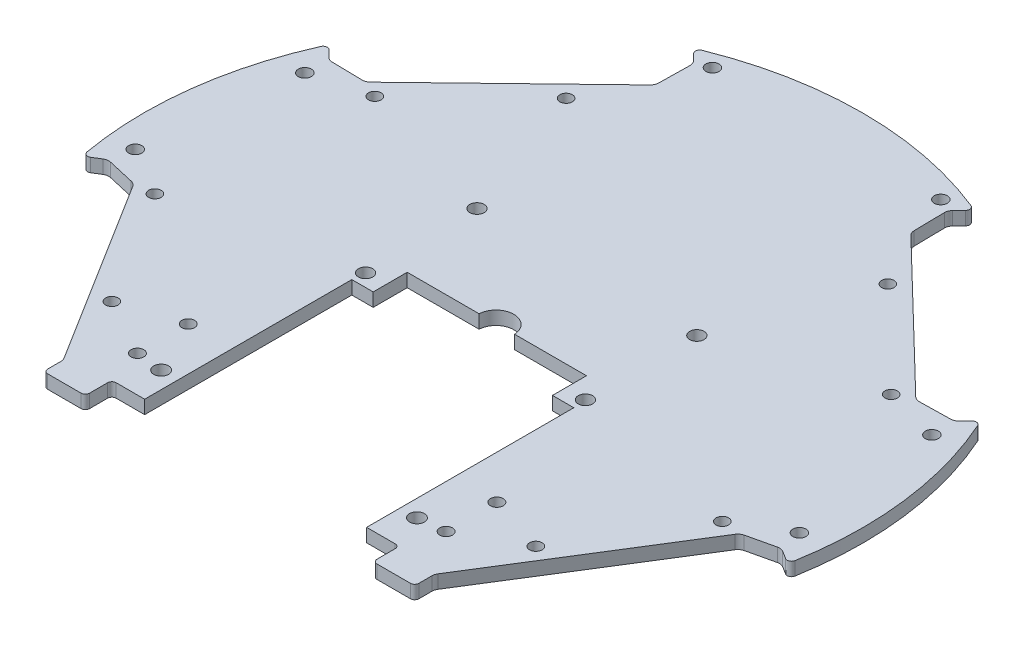
SolidWorks part; units mm, degrees
note: '?' marks a value the reader was unsure of.
material "6061 Alloy"
ref_plane "Front Plane" through (0, 0, 0) normal (0, 0, 1) x (1, 0, 0)
ref_plane "Top Plane" through (0, 0, 0) normal (0, 1, 0) x (1, 0, 0)
ref_plane "Right Plane" through (0, 0, 0) normal (1, 0, 0) x (0, 0, -1)
sketch "Sketch1" plane through (0, 0, 0) normal (0, 1, 0) x (1, 0, 0)
  line L0 (0, 0) -> (0, -59.55) construction
  line L1 (-83.4462, -16.178) -> (-71.2857, -8.5793) construction
  line L6 (0, 0) -> (-59.046, 61.1439) construction
  line L7 (0, 0) -> (-72.0841, -45.0431) construction
  line L8 (-33.174, 78.2591) -> (-23.2129, 67.9442) construction
  line L9 (-72.0841, -45.0431) -> (-70.388, -43.9833) construction
  line L10 (-70.388, -43.9833) -> (-84.9608, -20.662) construction
  line L11 (-84.9608, -20.662) -> (-72.2401, -12.7132) construction
  line L12 (-72.2401, -12.7132) -> (-43.0945, -59.3558) construction
  line L13 (-43.0945, -59.3558) -> (-55.8152, -67.3046) construction
  line L14 (-55.8152, -67.3046) -> (-70.388, -43.9833) construction
  line L21 (-59.046, 61.1439) -> (-57.6566, 59.7052)
  line L22 (-77.4385, 40.6021) -> (-37.8748, 78.8083) construction
  line L23 (-73.9694, 32.6911) -> (-77.0537, 35.885)
  line L24 (-37.8748, 78.8083) -> (-27.4549, 68.0182) construction
  line L25 (-27.4549, 68.0182) -> (-67.0186, 29.812) construction
  line L26 (-67.0186, 29.812) -> (-77.4385, 40.6021) construction
  line L27 (-43.0945, -64.8266) -> (-34, -64.8266)
  line L33 (-86.5505, -18.1178) -> (-71.2857, -8.5793) construction
  line L34 (0, 0) -> (0, 50000) construction
  line L35 (0, 0) -> (-50000, 0) construction
  line L36 (-60.6531, -59.55) -> (-19.8595, -59.55) construction
  line L38 (-67.0927, 25.57) -> (-79.5965, 38.5181) construction
  line L39 (-54.9774, -64.8266) -> (0, -64.8266) construction
  line L40 (-35.7168, 80.8923) -> (-23.2129, 67.9442) construction
  line L41 (-38.9606, -60.3102) -> (-54.2255, -69.8488) construction
  line L42 (-34, -59.55) -> (-19.8595, -59.55) construction
  line L43 (-43.0945, -64.8266) -> (-43.0945, -58.4123) construction
  line L45 (73.9694, 32.6911) -> (77.0537, 35.885)
  line L46 (-71.2857, -8.5793) -> (-38.9606, -60.3102) construction
  line L47 (83.4462, -16.178) -> (79.6809, -13.8252)
  line L48 (69.4846, -16.1792) -> (43.8945, -57.132)
  line L50 (43.0945, -64.8266) -> (34, -64.8266)
  line L51 (34, -59.55) -> (34, -64.8266)
  line L52 (0, 0) -> (72.0841, -45.0431) construction
  line L53 (0, 0) -> (59.046, 61.1439) construction
  line L54 (-30.0897, 75.0653) -> (-30.2847, 63.8954)
  line L55 (-62.7996, 32.4961) -> (-30.2847, 63.8954)
  line L56 (-30.0897, 75.0653) -> (-33.174, 78.2591)
  line L57 (73.9694, 32.6911) -> (77.0537, 35.885)
  line L58 (30.0897, 75.0653) -> (33.174, 78.2591)
  line L59 (-34, -59.55) -> (-34, -58.55)
  line L60 (62.7996, 32.4961) -> (30.2847, 63.8954)
  line L61 (-73.9694, 32.6911) -> (-62.7996, 32.4961)
  line L62 (-77.0537, 35.885) -> (-67.0927, 25.57) construction
  line L63 (-83.4462, -16.178) -> (-79.6809, -13.8252)
  line L64 (-79.6809, -13.8252) -> (-69.4846, -16.1792)
  line L65 (-69.4846, -16.1792) -> (-43.8945, -57.132)
  line L66 (-27.4549, 68.0182) -> (-23.2129, 67.9442) construction
  line L67 (-72.2401, -12.7132) -> (-71.2857, -8.5793) construction
  line L68 (30.0897, 75.0653) -> (30.2847, 63.8954)
  line L69 (73.9694, 32.6911) -> (62.7996, 32.4961)
  line L70 (-34, -59.55) -> (-34, -64.8266)
  line L71 (79.6809, -13.8252) -> (69.4846, -16.1792)
  line L72 (-34, -58.55) -> (-20, -58.55)
  line L73 (-20, -58.55) -> (-19.8595, -59.55)
  line L74 (-19.8595, -59.55) -> (19.8595, -59.55)
  line L75 (20, -58.55) -> (19.8595, -59.55)
  line L76 (34, -58.55) -> (20, -58.55)
  line L77 (34, -59.55) -> (34, -58.55)
  line L78 (-43.0945, -64.8266) -> (-43.8945, -64.8266)
  line L79 (-19.8595, -59.55) -> (0, -59.55) construction
  line L80 (-19.8595, -59.55) -> (34, -59.55) construction
  line L81 (-43.8945, -64.8266) -> (-43.8945, -57.132)
  line L82 (-43.0945, -58.4123) -> (-43.8945, -57.132) construction
  line L83 (43.8945, -64.8266) -> (43.8945, -57.132)
  line L84 (43.0945, -64.8266) -> (43.8945, -64.8266)
  line L97 (-23.2129, 67.9442) -> (-67.0927, 25.57) construction
  circle A0 centre (0, 0) radius 85 construction
  circle A1 centre (0, 0) radius 90 construction
  arc A51 (-77.0537, 35.885) -> (-83.4462, -16.178) centre (0, 0) ccw
  arc A52 (77.0537, 35.885) -> (83.4462, -16.178) centre (0, 0) cw
  arc A54 (-33.174, 78.2591) -> (33.174, 78.2591) centre (0, 0) cw
  point P29 (-31.6318, 76.6622)
  point P33 (-47.2368, 48.9151)
  point P34 (31.6318, 76.6622)
  point P35 (-57.6673, -36.0345)
  point P85 (-57.6566, 59.7052)
  dimension "D2" = 58
  dimension "D10" = 82
  dimension "D12" = 170
  dimension "D14" = 34
  dimension "D13" = 1
  dimension "D15" = 3
  dimension "D3" = 180
  dimension "D4" = 64.8266
  dimension "D5" = 44
  dimension "D6" = 15
  dimension "D7" = 55
  dimension "D8" = 59.55
  dimension "D9" = 2
  dimension "D11" = 2
  dimension "D16" = 7
  dimension "D17" = 7
  dimension "D18" = 0.5
  dimension "D19" = 1
  dimension "D20" = 14
  dimension "D21" = 0.8
extrude "Boss-Extrude4" add sketch "Sketch1" along normal mid plane 3.175
ref_point "Rear_Axle_Center (L)"
ref_axis "Rear_Axle_Proj (L)" through (46.5421, 0, -48.1958) along (0, 1, 0)?
ref_point "Front_Axle_Center (L)"
ref_axis "Front_Axle_Proj (L)" through (57.2432, 0, 35.7696) along (0, 1, 0)?
ref_point "Front_Axle_Center (R)"
ref_axis "Front_Axle_Proj (R)" through (-57.2432, 0, 35.7696) along (0, 1, 0)?
ref_point "Read_Axle_Center (R)"
ref_axis "Rear_Axle_Proj (R)" through (-46.5421, 0, -48.1958) along (0, 1, 0)?
sketch "Sketch17" plane through (0, 1.5875, 0) normal (0, 1, 0) x (1, 0, 0)
  line L0 (0, -54.55) -> (0, -59.55) construction
  line L1 (-19.8595, -59.55) -> (19.8595, -59.55) construction
  circle A0 centre (0, -54.55) radius 8.5
  dimension "D1" = 17
  dimension "D2" = 5
extrude "Boss-Extrude5" [suppressed] add sketch "Sketch17" against normal up to surface (3.175 mm away)
ref_plane "Plane1" through (0, 0, 10) normal (0, 0, 1) x (1, 0, 0)
hole_wizard "M3 Clearance Hole3" positions "Sketch18" profile "Sketch19" hole size "M3" standard "ANSI Metric" end condition through all
sketch "Sketch18" plane through (0, -1.5875, 0) normal (0, -1, 0) x (-1, 0, 0)
  line L0 (-36.5, -50) -> (-36.5, -38) construction
  line L3 (0, 0) -> (0, -38) construction
  line L4 (36.5, -50) -> (36.5, -38) construction
  line L6 (0, -38) -> (36.5, -38) construction
  line L8 (0, -38) -> (-36.5, -38) construction
  line L9 (-36.5, -44) -> (36.5, -44) construction
  line L10 (0, -44) -> (0, 0) construction
  point P1 (36.5, -50)
  point P3 (36.5, -38)
  point P5 (-36.5, -50)
  point P33 (-36.5, -38)
  dimension "D1" = 12
  dimension "D2" = 73
  dimension "D4" = 38
sketch "Sketch19" plane through (-36.5, -1.5875, 50) normal (1, 0, 0) x (0, 0, -1)
  line L0 (0, 0) -> (0, 3.175)
  line L1 (0, 3.175) -> (1.5, 3.175)
  line L2 (1.5, 3.175) -> (1.5, 0)
  line L5 (1.5, 0) -> (0, 0)
  line L11 (0, -6.35) -> (0, 107.95) construction
  dimension "Thru Hole Dia." = 3
  dimension "Thru Hole Depth" = 3.175
hole_wizard "M3 Clearance Hole1" positions "Sketch11" profile "Sketch12" hole size "M3" standard "ANSI Metric" end condition through all
sketch "Sketch11" plane through (0, 1.5875, 0) normal (0, 1, 0) x (1, 0, 0)
  line L0 (83.4462, -16.178) -> (79.6809, -13.8252) construction
  line L2 (73.9694, 32.6911) -> (77.0537, 35.885) construction
  line L4 (-73.9694, 32.6911) -> (-77.0537, 35.885) construction
  line L6 (0, 0) -> (0, -50000) construction
  line L7 (78.4111, 9.6277) -> (84.3664, 10.3589) construction
  line L10 (74.155, 27.2403) -> (78.5423, -8.4914) construction
  line L12 (78.4111, 9.6277) -> (76.3487, 9.3744) construction
  arc A7 (77.964, -12.7523) -> (72.563, 31.2347) centre (0, 0) ccw construction
  arc A13 (-77.964, -12.7523) -> (-72.563, 31.2347) centre (0, 0) cw construction
  arc A17 (83.4462, -16.178) -> (77.0537, 35.885) centre (0, 0) ccw construction
  point P34 (78.5423, -8.4914)
  point P66 (74.155, 27.2403)
  point P70 (-74.155, 27.2403)
  point P71 (-78.5423, -8.4914)
  dimension "D1" = 6
  dimension "D2" = 36
sketch "Sketch12" plane through (-78.5423, 1.5875, 8.4914) normal (1, 0, 0) x (0, 0, 1)
  line L0 (0, 0) -> (0, 3.175)
  line L1 (0, 3.175) -> (1.55, 3.175)
  line L2 (1.55, 3.175) -> (1.55, 0)
  line L5 (1.55, 0) -> (0, 0)
  line L11 (0, -6.35) -> (0, 107.95) construction
  dimension "Thru Hole Dia." = 3.1
  dimension "Thru Hole Depth" = 3.175
hole_wizard "M3 Clearance Hole4" positions "Sketch9" profile "Sketch10" hole size "M3" standard "ANSI Metric" end condition through all
sketch "Sketch9" plane through (0, -1.5875, 0) normal (0, -1, 0) x (-1, 0, 0)
  line L0 (0, 0) -> (0, 63.4318) construction
  line L1 (-38.0437, 52.9272) -> (38.0437, 52.9272) construction
  line L3 (61.0625, 30.6981) -> (-61.0625, 30.6981) construction
  line L4 (-67.0993, -15.2789) -> (67.0993, -15.2789) construction
  line L5 (50.1419, -42.4164) -> (-50.1419, -42.4164) construction
  line L6 (-61.0625, 30.6981) -> (-38.0437, 52.9272) construction
  line L7 (38.0437, 52.9272) -> (61.0625, 30.6981) construction
  line L8 (67.0993, -15.2789) -> (50.1419, -42.4164) construction
  line L9 (-50.1419, -42.4164) -> (-67.0993, -15.2789) construction
  line L10 (0, 0) -> (-44.8055, 46.3974) construction
  line L11 (0, 0) -> (44.8055, 46.3974) construction
  line L12 (0, 0) -> (-96.9468, 0) construction
  line L14 (-55.1231, -34.4448) -> (0, 0) construction
  line L15 (0, 0) -> (55.1231, -34.4448) construction
  line L18 (-69.4846, -16.1792) -> (-43.8945, -57.132) construction
  line L19 (-62.7996, 32.4961) -> (-30.2847, 63.8954) construction
  point P0 (-67.0993, -15.2789)
  point P2 (-50.1419, -42.4164)
  point P9 (-61.0625, 30.6981)
  point P11 (-38.0437, 52.9272)
  point P30 (50.1419, -42.4164)
  point P31 (67.0993, -15.2789)
  point P32 (38.0437, 52.9272)
  point P33 (61.0625, 30.6981)
  dimension "D9" = 46
  dimension "D10" = 46
  dimension "D11" = 32
  dimension "D12" = 32
  dimension "D7" = 58
  dimension "D5" = 32
  dimension "D6" = 2.5
  dimension "D8" = 9.4
  dimension "D2" = 44
  dimension "D3" = 32
  dimension "D4" = 2.5
  dimension "D13" = 9.4
sketch "Sketch10" plane through (67.0993, -1.5875, 15.2789) normal (1, 0, 0) x (0, 0, -1)
  line L0 (0, 0) -> (0, 3.175)
  line L1 (0, 3.175) -> (1.475, 3.175)
  line L2 (1.475, 3.175) -> (1.475, 0)
  line L5 (1.475, 0) -> (0, 0)
  line L11 (0, -6.35) -> (0, 107.95) construction
  dimension "Thru Hole Dia." = 2.95
  dimension "Thru Hole Depth" = 3.175
hole_wizard "M3 Clearance Hole2" positions "Sketch13" profile "Sketch14" hole size "M3" standard "ANSI Metric" end condition through all
sketch "Sketch13" plane through (0, 1.5875, 0) normal (0, 1, 0) x (1, 0, 0)
  line L0 (0, 0) -> (0, 85) construction
  line L2 (-24, 47) -> (-24, 81) construction
  line L3 (-24, 47) -> (24, 47) construction
  line L4 (-24, 81) -> (24, 81) construction
  line L5 (24, 47) -> (24, 81) construction
  line L6 (-24, 47) -> (24, 81) construction
  line L7 (-24, 81) -> (24, 47) construction
  line L8 (-38.0437, 52.9272) -> (-61.0625, 30.6981) construction
  line L10 (-36.307, 51.1289) -> (-59.3259, 28.8998) construction
  line L11 (-16.3488, 39.8187) -> (-31.6313, 55.6441) construction
  line L12 (-16.3488, 39.8187) -> (-48.7191, 8.559) construction
  line L13 (-31.6313, 55.6441) -> (-64.0016, 24.3845) construction
  line L14 (-48.7191, 8.559) -> (-64.0016, 24.3845) construction
  line L15 (-16.3488, 39.8187) -> (-64.0016, 24.3845) construction
  line L16 (-31.6313, 55.6441) -> (-48.7191, 8.559) construction
  line L17 (-49.5531, 41.8127) -> (-40.1752, 32.1016) construction
  line L18 (-27, 76.4978) -> (-27, 80.5978) construction
  arc A0 (33.174, 78.2591) -> (-33.174, 78.2591) centre (0, 0) ccw construction
  circle A1 centre (-16.2162, 44) radius 3 construction
  circle A2 centre (-27, 76.4978) radius 3 construction
  point P65 (0, 64)
  point P181 (-27, 76.4978)
  point P184 (27, 76.4978)
  dimension "D7" = 6
  dimension "D1" = 48
  dimension "D2" = 34
  dimension "D3" = 4
  dimension "D5" = 45
  dimension "D6" = 22
  dimension "D8" = 4.1
  dimension "D4" = 2.5
sketch "Sketch14" plane through (27, 1.5875, -76.4978) normal (1, 0, 0) x (0, 0, 1)
  line L0 (0, 0) -> (0, 3.175)
  line L1 (0, 3.175) -> (1.55, 3.175)
  line L2 (1.55, 3.175) -> (1.55, 0)
  line L5 (1.55, 0) -> (0, 0)
  line L11 (0, -6.35) -> (0, 107.95) construction
  dimension "Thru Hole Dia." = 3.1
  dimension "Thru Hole Depth" = 3.175
hole_wizard "M3 Clearance Hole5" [suppressed] positions "Sketch24" profile "Sketch25" hole size "M3" standard "ANSI Metric"
sketch "Sketch24" plane through (0, 1.5875, 0) normal (0, 1, 0) x (1, 0, 0)
  line L1 (-11, -4.4) -> (11, -4.4) construction
  line L2 (11, -4.4) -> (11, -36.4) construction
  line L3 (11, -36.4) -> (-11, -36.4) construction
  line L4 (-11, -36.4) -> (-11, -4.4) construction
  line L7 (-11, 37.6) -> (11, 37.6) construction
  line L8 (0, -4.4) -> (0, 0) construction
  line L9 (0, 0) -> (0, 37.6) construction
  point P8 (-11, -4.4)
  point P10 (11, -4.4)
  point P12 (11, -36.4)
  point P14 (-11, -36.4)
  point P42 (-11, 37.6)
  point P45 (11, 37.6)
  dimension "D1" = 22
  dimension "D2" = 32
  dimension "D3" = 4.4
  dimension "D4" = 42
sketch "Sketch25" plane through (-11, 1.5875, 4.4) normal (1, 0, 0) x (0, 0, 1)
  line L0 (0, 0) -> (0, 3.175)
  line L1 (0, 3.175) -> (1.5, 3.175)
  line L2 (1.5, 3.175) -> (1.5, 0)
  line L5 (1.5, 0) -> (0, 0)
  line L11 (0, -6.35) -> (0, 107.95) construction
  dimension "Thru Hole Dia." = 3
  dimension "Thru Hole Depth" = 3.175
sketch "Sketch20" plane through (0, 1.5875, 0) normal (0, 1, 0) x (1, 0, 0)
  line L0 (-16.1485, 44) -> (-16.1485, 39) construction
  line L1 (-14.6485, 44) -> (-14.6485, 39)
  line L2 (-17.6485, 44) -> (-17.6485, 39)
  line L3 (0, 0) -> (0, 85) construction
  line L5 (16.1485, 44) -> (16.1485, 39) construction
  line L6 (14.6485, 44) -> (14.6485, 39)
  line L7 (17.6485, 44) -> (17.6485, 39)
  arc A0 (-14.6485, 44) -> (-17.6485, 44) centre (-16.1485, 44) ccw
  arc A1 (-17.6485, 39) -> (-14.6485, 39) centre (-16.1485, 39) ccw
  arc A5 (33.174, 78.2591) -> (-33.174, 78.2591) centre (0, 0) ccw construction
  arc A7 (14.6485, 44) -> (17.6485, 44) centre (16.1485, 44) cw
  arc A8 (17.6485, 39) -> (14.6485, 39) centre (16.1485, 39) cw
  point P2 (-16.1485, 41.5)
  point P16 (16.1485, 41.5)
  dimension "D1" = 44
  dimension "D2" = 3
  dimension "D3" = 5
  dimension "D4" = 16.1485
extrude "Cut-Extrude1" [suppressed] cut sketch "Sketch20" against normal through all
sketch "Sketch22" plane through (0, 1.5875, 0) normal (0, 1, 0) x (1, 0, 0)
  line L0 (-56.6896, -36.6556) -> (-58.0464, -37.5035) construction
  line L1 (-69.4846, -16.1792) -> (-43.8945, -57.132) construction
  line L3 (30.2452, 66.1578) -> (65.062, 32.5356)
  line L4 (71.6894, -15.6702) -> (43.8945, -60.1514)
  line L5 (-19.8595, -59.55) -> (19.8595, -59.55) construction
  line L6 (-43.8945, -64.8266) -> (-43.8945, -57.132) construction
  line L28 (-30.2452, 66.1578) -> (-65.062, 32.5356)
  line L29 (-71.6894, -15.6702) -> (-43.8945, -60.1514)
  line L30 (-79.6809, -13.8252) -> (-69.4846, -16.1792) construction
  line L31 (0, 85) -> (0, -59.55) construction
  line L32 (-46.5421, 48.1958) -> (-47.6536, 49.3467) construction
  line L37 (-20, -58.55) -> (-19.8595, -59.55)
  line L38 (-20, -58.55) -> (-19.8595, -59.55)
  line L40 (-43.8945, -57.132) -> (-43.8945, -64.8266)
  line L41 (-43.8945, -57.132) -> (-43.8945, -64.8266)
  line L43 (43.8945, -64.8266) -> (43.8945, -57.132)
  line L44 (43.8945, -64.8266) -> (43.8945, -57.132)
  line L56 (-19.8595, -59.55) -> (19.8595, -59.55)
  line L58 (19.8595, -59.55) -> (20, -58.55)
  line L59 (20, -58.55) -> (34, -58.55)
  line L60 (34, -58.55) -> (34, -64.8266)
  line L61 (34, -64.8266) -> (43.8945, -64.8266)
  line L63 (43.8945, -57.132) -> (69.4846, -16.1792)
  line L64 (69.4846, -16.1792) -> (79.6809, -13.8252)
  line L65 (79.6809, -13.8252) -> (83.4462, -16.178)
  line L66 (77.0537, 35.885) -> (73.9694, 32.6911)
  line L67 (73.9694, 32.6911) -> (62.7996, 32.4961)
  line L68 (62.7996, 32.4961) -> (30.2847, 63.8954)
  line L69 (30.2847, 63.8954) -> (30.0897, 75.0653)
  line L70 (30.0897, 75.0653) -> (33.174, 78.2591)
  line L71 (-33.174, 78.2591) -> (-30.0897, 75.0653)
  line L72 (-30.0897, 75.0653) -> (-30.2847, 63.8954)
  line L73 (-30.2847, 63.8954) -> (-62.7996, 32.4961)
  line L74 (-62.7996, 32.4961) -> (-73.9694, 32.6911)
  line L75 (-73.9694, 32.6911) -> (-77.0537, 35.885)
  line L76 (-83.4462, -16.178) -> (-79.6809, -13.8252)
  line L77 (-79.6809, -13.8252) -> (-69.4846, -16.1792)
  line L78 (-69.4846, -16.1792) -> (-43.8945, -57.132)
  line L80 (-43.8945, -64.8266) -> (-34, -64.8266)
  line L81 (-34, -64.8266) -> (-34, -58.55)
  line L82 (-34, -58.55) -> (-20, -58.55)
  line L84 (-19.8595, -59.55) -> (19.8595, -59.55)
  line L86 (19.8595, -59.55) -> (20, -58.55)
  line L87 (20, -58.55) -> (34, -58.55)
  line L88 (34, -58.55) -> (34, -64.8266)
  line L89 (34, -64.8266) -> (43.8945, -64.8266)
  line L91 (43.8945, -57.132) -> (69.4846, -16.1792)
  line L92 (69.4846, -16.1792) -> (79.6809, -13.8252)
  line L93 (79.6809, -13.8252) -> (83.4462, -16.178)
  line L94 (77.0537, 35.885) -> (73.9694, 32.6911)
  line L95 (73.9694, 32.6911) -> (62.7996, 32.4961)
  line L96 (62.7996, 32.4961) -> (30.2847, 63.8954)
  line L97 (30.2847, 63.8954) -> (30.0897, 75.0653)
  line L98 (30.0897, 75.0653) -> (33.174, 78.2591)
  line L99 (-33.174, 78.2591) -> (-30.0897, 75.0653)
  line L100 (-30.0897, 75.0653) -> (-30.2847, 63.8954)
  line L101 (-30.2847, 63.8954) -> (-62.7996, 32.4961)
  line L102 (-62.7996, 32.4961) -> (-73.9694, 32.6911)
  line L103 (-73.9694, 32.6911) -> (-77.0537, 35.885)
  line L104 (-83.4462, -16.178) -> (-79.6809, -13.8252)
  line L105 (-79.6809, -13.8252) -> (-69.4846, -16.1792)
  line L106 (-69.4846, -16.1792) -> (-43.8945, -57.132)
  line L108 (-43.8945, -64.8266) -> (-34, -64.8266)
  line L109 (-34, -64.8266) -> (-34, -58.55)
  line L110 (-34, -58.55) -> (-20, -58.55)
  arc A9 (83.4462, -16.178) -> (77.0537, 35.885) centre (0, 0) ccw
  arc A10 (33.174, 78.2591) -> (-33.174, 78.2591) centre (0, 0) ccw
  arc A11 (-77.0537, 35.885) -> (-83.4462, -16.178) centre (0, 0) ccw
  arc A13 (83.4462, -16.178) -> (77.0537, 35.885) centre (0, 0) ccw
  arc A14 (33.174, 78.2591) -> (-33.174, 78.2591) centre (0, 0) ccw
  arc A15 (-77.0537, 35.885) -> (-83.4462, -16.178) centre (0, 0) ccw
  dimension "D2" = 1.6
  dimension "D1" = 0
extrude "Boss-Extrude6" add sketch "Sketch22" against normal up to surface (3.175 mm away) up to face at (-27, -1.5875, -74.9478)
fillet "Fillet1" radius 2 14 edges at (-30.0897, 0, -75.0653) (30.0897, 0, -75.0653) (-79.6809, 0, 13.8252) (79.6809, 0, 13.8252) (73.9694, 0, -32.6911) (-73.9694, 0, -32.6911) (65.062, 0, -32.5356) (30.2452, 0, -66.1578) (71.6894, 0, 15.6702) (-71.6894, 0, 15.6702) (-65.062, 0, -32.5356) (-30.2452, 0, -66.1578) (43.8945, 0, 60.1514) (-43.8945, 0, 60.1514)
fillet "Fillet3" radius 1 12 edges at (-77.0537, 0, -35.885) (77.0537, 0, -35.885) (83.4462, 0, 16.178) (34, 0, 64.8266) (-34, 0, 64.8266) (-33.174, 0, -78.2591) (33.174, 0, -78.2591) (-83.4462, 0, 16.178) (34, 0, 58.55) (-34, 0, 58.55) (-43.8945, 0, 64.8266) (43.8945, 0, 64.8266)
sketch "Sketch23" [suppressed] plane through (0, 3.175, 0) normal (0, 1, 0) x (1, 0, 0)
  circle A0 centre (0, -53.55) radius 4.95
  dimension "D1" = 9.9
fillet "Fillet6" radius 0.5 4 edges at (20, 0, 58.55) (19.8595, 0, 59.55) (-20, 0, 58.55) (-19.8595, 0, 59.55)
sketch "Sketch28" plane through (0, 1.5875, 0) normal (0, 1, 0) x (1, 0, 0)
  line L0 (-19.4248, -59.55) -> (19.4248, -59.55) construction
  line L1 (-19.4248, -59.55) -> (19.4248, -59.55) construction
  line L2 (-26.25, -59.55) -> (26.25, -59.55)
  line L3 (-26.25, -59.55) -> (-26.25, -9.55)
  line L4 (26.25, -59.55) -> (26.25, -9.55)
  line L5 (-26.25, -9.55) -> (26.25, -9.55)
  line L6 (0, -1.7) -> (0, -77.8833) construction
  line L7 (-21, -1.7) -> (-21, -9.55) construction
  line L8 (21, -1.7) -> (4, -1.7) construction
  line L9 (21, -1.7) -> (21, -9.55) construction
  line L10 (-4, -1.7) -> (-21, -1.7) construction
  line L11 (21.2, -1.5) -> (21.2, -9.55)
  line L12 (21.2, -1.5) -> (4.1952, -1.5)
  line L13 (-4.1952, -1.5) -> (-21.2, -1.5)
  line L14 (-21.2, -1.5) -> (-21.2, -9.55)
  arc A0 (19.4248, -59.55) -> (19.9199, -59.1196) centre (19.4248, -59.05) ccw construction
  arc A1 (4, -1.7) -> (-4, -1.7) centre (0, -1.7) ccw construction
  arc A2 (4.1952, -1.5) -> (-4.1952, -1.5) centre (0, -1.7) ccw
  point P11 (0, -59.55)
  point P16 (0, -9.55)
  point P23 (0, -1.7)
  dimension "D4" = 4
  dimension "D1" = 52.5
  dimension "D2" = 50
  dimension "D3" = 17
  dimension "D5" = 7.85
extrude "Cut-Extrude4" cut sketch "Sketch28" against normal blind 10 contours L8 A1 L10 L7 L5 L9 | L5 L3 L2 L4
extrude "Cut-Extrude2" [suppressed] cut sketch "Sketch23" against normal through all
sketch "Sketch26" [suppressed] plane through (0, 3.175, 0) normal (0, 1, 0) x (1, 0, 0)
  line L0 (0, 0) -> (0, 50) construction
  line L1 (-92.5, 5) -> (92.5, 5)
  line L2 (-92.5, 5) -> (-92.5, 95)
  line L3 (-92.5, 95) -> (92.5, 95)
  line L4 (92.5, 5) -> (92.5, 95)
  line L5 (-92.5, 5) -> (92.5, 95) construction
  line L6 (-92.5, 95) -> (92.5, 5) construction
  point P0 (0, 50)
  dimension "D1" = 90
  dimension "D2" = 185
  dimension "D3" = 5
extrude "Cut-Extrude3" [suppressed] cut sketch "Sketch26" against normal through all
fillet "Fillet4" [suppressed] radius 5
sketch "Sketch29" plane through (0, 1.5875, 0) normal (0, 1, 0) x (1, 0, 0)
  line L0 (-33, -58.55) -> (-26.25, -58.55) construction
  line L1 (0, -81.301) -> (0, 102.6168) construction
  line L2 (-26.25, -9.55) -> (-26.25, -58.55) construction
  line L3 (-26.25, -50.65) -> (-32.5626, -50.65) construction
  line L4 (-26.25, -50.65) -> (-30.25, -50.65)
  circle A0 centre (30.25, -50.65) radius 1.75
  circle A1 centre (-30.25, -50.65) radius 1.75
  dimension "D5" = 3.5
  dimension "D1" = 7.9
  dimension "D2" = 30.25
extrude "Cut-Extrude5" cut sketch "Sketch29" against normal blind 10
sketch "Sketch31" plane through (0, 1.5875, 0) normal (0, 1, 0) x (1, 0, 0)
  line L0 (26.25, -9.55) -> (21.2, -9.55) construction
  line L1 (0, 35.8655) -> (0, -81.8862) construction
  line L2 (-26, -6.55) -> (-26, 19.8) construction
  circle A0 centre (-26, -6.55) radius 1.7
  circle A1 centre (26, -6.55) radius 1.7
  circle A2 centre (-26, 19.8) radius 1.7
  circle A3 centre (26, 19.8) radius 1.7
  dimension "D3" = 3.4
  dimension "D1" = 52
  dimension "D2" = 3
  dimension "D4" = 26.35
extrude "Cut-Extrude7" cut sketch "Sketch31" against normal blind 10
sketch "Sketch32" plane through (0, 1.5875, 0) normal (0, 1, 0) x (1, 0, 0)
  line L0 (-43.6016, -64.5337) -> (43.6016, -64.5337)
  line L1 (-43.6016, -64.5337) -> (-43.6016, 20.2064)
  line L2 (43.6016, -64.5337) -> (43.6016, 20.2064)
  line L3 (-43.6016, 20.2064) -> (43.6016, 20.2064)
  arc A0 (-43.8945, -63.8266) -> (-42.8945, -64.8266) centre (-42.8945, -63.8266) ccw construction
  arc A1 (42.8945, -64.8266) -> (43.8945, -63.8266) centre (42.8945, -63.8266) ccw construction
extrude "Cut-Extrude8" [suppressed] cut sketch "Sketch32" against normal blind 10 flip side to cut
sketch "Sketch33" [suppressed] plane through (0, -1.5875, 0) normal (0, -1, 0) x (1, 0, 0)
  line L0 (-43.6016, 64.5337) -> (-34.2929, 64.5337)
  line L1 (-43.6016, 64.5337) -> (-43.6016, 54.5337)
  line L2 (-34.2929, 64.5337) -> (-34.2929, 54.5337)
  line L3 (-43.6016, 54.5337) -> (-34.2929, 54.5337)
  line L4 (43.6016, 64.5337) -> (34.2929, 64.5337)
  line L5 (43.6016, 64.5337) -> (43.6016, 54.5337)
  line L6 (34.2929, 64.5337) -> (34.2929, 54.5337)
  line L7 (43.6016, 54.5337) -> (34.2929, 54.5337)
  line L9 (-43.6016, -20.2064) -> (-33.6016, -20.2064)
  line L10 (-43.6016, -20.2064) -> (-43.6016, -10.2064)
  line L11 (-43.6016, -10.2064) -> (-33.6016, -10.2064)
  line L12 (-33.6016, -20.2064) -> (-33.6016, -10.2064)
  line L13 (43.6016, -20.2064) -> (33.6016, -20.2064)
  line L14 (43.6016, -20.2064) -> (43.6016, -10.2064)
  line L15 (43.6016, -10.2064) -> (33.6016, -10.2064)
  line L16 (33.6016, -20.2064) -> (33.6016, -10.2064)
  dimension "D1" = 10
  dimension "D2" = 10
  dimension "D3" = 10
  dimension "D4" = 10
  dimension "D5" = 10
  dimension "D6" = 10
extrude "Boss-Extrude7" [suppressed] add sketch "Sketch33" along normal blind 5
equation "\"D3@Sketch9\"=\"D5@Sketch9\""
equation "\"D4@Sketch9\"=\"D6@Sketch9\""
equation "\"D13@Sketch9\"=\"D8@Sketch9\""
equation "\"D1@Sketch28\"=54.000000mm-1.5"
